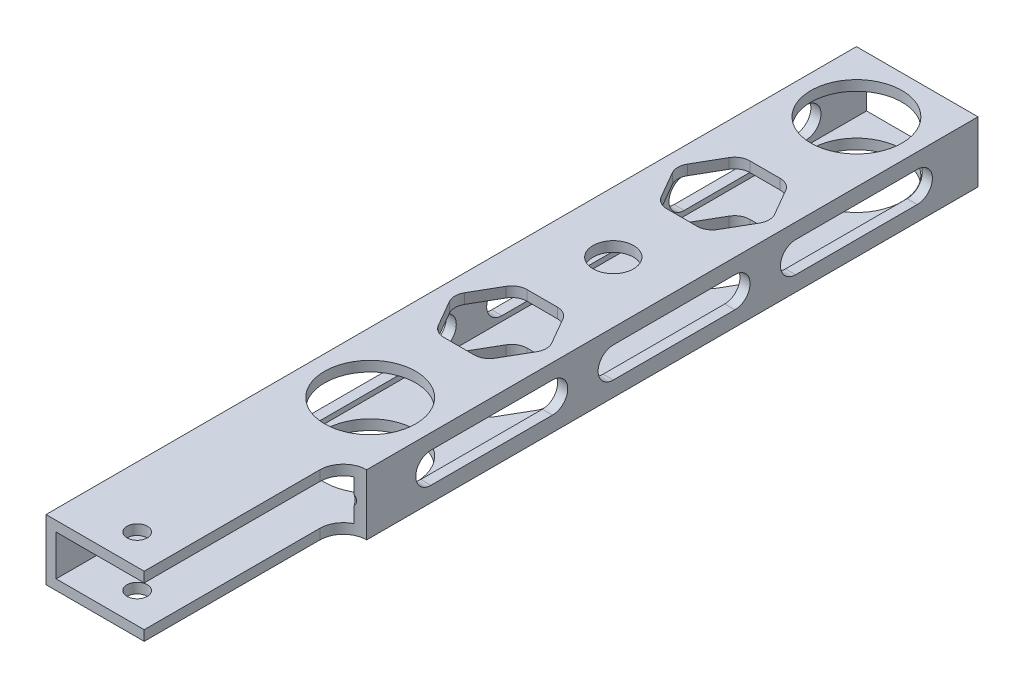
SolidWorks part; units mm, degrees
material "6063-T6"
ref_plane "Front" through (0, 0, 0) normal (0, 0, 1) x (1, 0, 0)
ref_plane "Top" through (0, 0, 0) normal (0, 1, 0) x (1, 0, 0)
ref_plane "Right" through (0, 0, 0) normal (1, 0, 0) x (0, 0, -1)
sketch "Sketch1" plane through (0, 0, 0) normal (0, 0, 1) x (1, 0, 0)
  line L0 (3.175, 3.175) -> (34.925, 3.175)
  line L1 (0, 0) -> (38.1, 0)
  line L2 (0, 0) -> (0, 19.05)
  line L3 (0, 19.05) -> (38.1, 19.05)
  line L4 (38.1, 0) -> (38.1, 19.05)
  line L5 (34.925, 3.175) -> (34.925, 15.875)
  line L6 (3.175, 15.875) -> (34.925, 15.875)
  line L7 (3.175, 3.175) -> (3.175, 15.875)
  dimension "D1" = 19.05
  dimension "D2" = 38.1
  dimension "D3" = 3.175
extrude "Boss-Extrude1" add sketch "Sketch1" along normal blind 254
sketch "Sketch2" plane through (0, 19.05, 0) normal (0, 1, 0) x (1, 0, 0)
  line L0 (19.05, 0) -> (19.05, -19.05) construction
  line L2 (19.05, -19.05) -> (19.05, -171.45) construction
  line L4 (38.1, -254) -> (38.1, 0) construction
  line L5 (38.1, 0) -> (0, 0) construction
  circle A0 centre (19.05, -19.05) radius 14.2875
  circle A1 centre (19.05, -171.45) radius 14.2875
  dimension "D1" = 28.575
  dimension "D4" = 28.575
  dimension "D2" = 19.05
  dimension "D3" = 152.4
  dimension "D5" = 19.05
extrude "Cut-Extrude1" cut sketch "Sketch2" against normal through all
sketch "Sketch3" plane through (0, 19.05, 0) normal (0, 1, 0) x (1, 0, 0)
  line L0 (19.05, -244.475) -> (19.05, -254) construction
  line L1 (38.1, -254) -> (0, -254) construction
  circle A0 centre (19.05, -244.475) radius 3.175
  dimension "D1" = 6.35
  dimension "D2" = 9.525
extrude "Cut-Extrude2" cut sketch "Sketch3" against normal through all
sketch "Sketch4" plane through (0, 19.05, 0) normal (0, 1, 0) x (1, 0, 0)
  line L0 (30.7745, -254) -> (30.7745, -198.9198)
  line L1 (38.1, -254) -> (0, -254) construction
  line L2 (38.1, -191.5943) -> (38.1, -254)
  line L3 (38.1, -254) -> (38.1, 0) construction
  line L4 (38.1, -254) -> (30.7745, -254)
  arc A0 (38.1, -191.5943) -> (30.7745, -198.9198) centre (38.1, -198.9198) ccw
extrude "Cut-Extrude3" cut sketch "Sketch4" against normal through all
sketch "Sketch5" plane through (0, 0, 0) normal (0, -1, 0) x (1, 0, 0)
  circle A0 centre (19.05, 95.25) radius 2.667 construction
  circle A1 centre (19.05, 95.25) radius 2.667
extrude "Cut-Extrude4" cut sketch "Sketch5" against normal through all
sketch "Sketch6" plane through (0, 19.05, 0) normal (0, 1, 0) x (1, 0, 0)
  circle A0 centre (19.05, -95.25) radius 6.35
  circle A1 centre (19.05, -95.25) radius 2.667 construction
  dimension "D1" = 12.7
sketch "Sketch7" plane through (0, 0, 0) normal (-1, 0, 0) x (0, 0, 1)
  line L0 (19.05, 9.525) -> (57.15, 9.525) construction
  line L1 (19.05, 14.2875) -> (57.15, 14.2875)
  line L2 (19.05, 4.7625) -> (57.15, 4.7625)
  line L3 (34.9537, 14.2875) -> (34.9537, 19.05) construction
  line L4 (254, 19.05) -> (0, 19.05) construction
  line L5 (40.4377, 4.7625) -> (40.4377, 0) construction
  line L6 (254, 0) -> (0, 0) construction
  line L7 (0, 19.05) -> (0, 0) construction
  line L8 (92.1037, 14.2875) -> (92.1037, 19.05) construction
  line L9 (97.5877, 4.7625) -> (97.5877, 0) construction
  line L10 (76.2, 9.525) -> (114.3, 9.525) construction
  line L11 (76.2, 14.2875) -> (114.3, 14.2875)
  line L12 (76.2, 4.7625) -> (114.3, 4.7625)
  line L13 (149.2537, 14.2875) -> (149.2537, 19.05) construction
  line L14 (154.7377, 4.7625) -> (154.7377, 0) construction
  line L15 (133.35, 9.525) -> (171.45, 9.525) construction
  line L18 (133.35, 14.2875) -> (171.45, 14.2875)
  line L19 (133.35, 4.7625) -> (171.45, 4.7625)
  line L20 (196.85, 9.525) -> (234.95, 9.525) construction
  line L22 (196.85, 14.2875) -> (234.95, 14.2875)
  line L23 (196.85, 4.7625) -> (234.95, 4.7625)
  arc A0 (19.05, 14.2875) -> (19.05, 4.7625) centre (19.05, 9.525) ccw
  arc A1 (57.15, 4.7625) -> (57.15, 14.2875) centre (57.15, 9.525) ccw
  arc A2 (76.2, 14.2875) -> (76.2, 4.7625) centre (76.2, 9.525) ccw
  arc A3 (114.3, 4.7625) -> (114.3, 14.2875) centre (114.3, 9.525) ccw
  arc A6 (133.35, 14.2875) -> (133.35, 4.7625) centre (133.35, 9.525) ccw
  arc A7 (171.45, 4.7625) -> (171.45, 14.2875) centre (171.45, 9.525) ccw
  arc A8 (196.85, 14.2875) -> (196.85, 4.7625) centre (196.85, 9.525) ccw
  arc A9 (234.95, 4.7625) -> (234.95, 14.2875) centre (234.95, 9.525) ccw
  point P2 (38.1, 9.525)
  point P20 (95.25, 9.525)
  point P30 (152.4, 9.525)
  point P43 (215.9, 9.525)
  dimension "D1" = 9.525
  dimension "D2" = 38.1
  dimension "D3" = 19.05
  dimension "D5" = 19.05
  dimension "D6" = 25.4
  dimension "D7" = 38.1
  dimension "D4" = 3
extrude "Cut-Extrude6" cut sketch "Sketch7" against normal through all
sketch "Sketch8" plane through (0, 19.05, 0) normal (0, 1, 0) x (1, 0, 0)
  line L0 (19.05, -60.7208) -> (38.1, -60.7208) construction
  line L1 (5.4006, -63.102) -> (10.1631, -71.3509)
  line L2 (14.2875, -73.7322) -> (23.8125, -73.7322)
  line L3 (27.9369, -71.3509) -> (32.6994, -63.102)
  line L4 (32.6994, -58.3395) -> (27.9369, -50.0906)
  line L5 (23.8125, -47.7094) -> (14.2875, -47.7094)
  line L6 (10.1631, -50.0906) -> (5.4006, -58.3395)
  line L7 (38.1, -191.5943) -> (38.1, 0) construction
  line L8 (5.4006, -132.952) -> (10.1631, -141.2009)
  line L9 (14.2875, -143.5822) -> (23.8125, -143.5822)
  line L10 (27.9369, -141.2009) -> (32.6994, -132.952)
  line L11 (32.6994, -128.1895) -> (27.9369, -119.9406)
  line L12 (23.8125, -117.5594) -> (14.2875, -117.5594)
  line L13 (10.1631, -119.9406) -> (5.4006, -128.1895)
  line L14 (19.05, -130.5708) -> (38.1, -130.5708) construction
  line L15 (0, -254) -> (0, 0) construction
  arc A0 (23.8125, -73.7322) -> (27.9369, -71.3509) centre (23.8125, -68.9697) ccw
  arc A1 (10.1631, -71.3509) -> (14.2875, -73.7322) centre (14.2875, -68.9697) ccw
  arc A2 (5.4006, -63.102) -> (5.4006, -58.3395) centre (9.525, -60.7208) cw
  arc A3 (14.2875, -47.7094) -> (10.1631, -50.0906) centre (14.2875, -52.4719) ccw
  arc A4 (27.9369, -50.0906) -> (23.8125, -47.7094) centre (23.8125, -52.4719) ccw
  arc A5 (32.6994, -63.102) -> (32.6994, -58.3395) centre (28.575, -60.7208) ccw
  arc A6 (23.8125, -143.5822) -> (27.9369, -141.2009) centre (23.8125, -138.8197) ccw
  arc A7 (10.1631, -141.2009) -> (14.2875, -143.5822) centre (14.2875, -138.8197) ccw
  arc A8 (5.4006, -132.952) -> (5.4006, -128.1895) centre (9.525, -130.5708) cw
  arc A9 (14.2875, -117.5594) -> (10.1631, -119.9406) centre (14.2875, -122.3219) ccw
  arc A10 (27.9369, -119.9406) -> (23.8125, -117.5594) centre (23.8125, -122.3219) ccw
  arc A11 (32.6994, -132.952) -> (32.6994, -128.1895) centre (28.575, -130.5708) ccw
  point P22 (34.0743, -60.7208)
  point P23 (0, 0)
  dimension "D1" = 4.7625
  dimension "D3" = 19.05
  dimension "D4" = 9.525
  dimension "D2" = 2
extrude "Cut-Extrude7" cut sketch "Sketch8" against normal through all
extrude "Cut-Extrude8" cut sketch "Sketch6" against normal up to next
